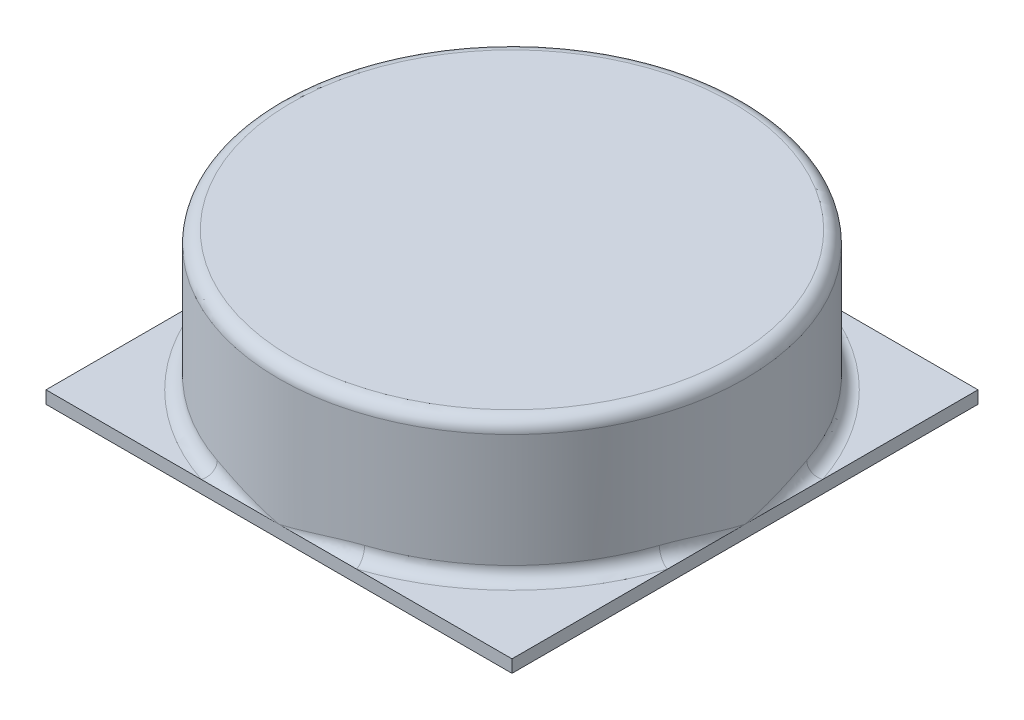
SolidWorks part; units mm, degrees
material "Inertia Wheel"
ref_plane "Piano frontale" through (0, 0, 0) normal (0, 0, 1) x (1, 0, 0)
ref_plane "Piano superiore" through (0, 0, 0) normal (0, 1, 0) x (1, 0, 0)
ref_plane "Piano destro" through (0, 0, 0) normal (1, 0, 0) x (0, 0, -1)
sketch "Schizzo1" plane through (0, 0, 0) normal (0, 1, 0) x (1, 0, 0)
  line L1 (-185, 185) -> (185, 185)
  line L2 (-185, 185) -> (-185, -185)
  line L3 (-185, -185) -> (185, -185)
  line L4 (185, 185) -> (185, -185)
  line L5 (-185, 185) -> (185, -185) construction
  line L6 (-185, -185) -> (185, 185) construction
  point P0 (0, 0)
  dimension "D1" = 370
extrude "Estrusione-Estrusione1" add sketch "Schizzo1" along normal blind 10
sketch "Schizzo2" plane through (0, 10, 0) normal (0, 1, 0) x (1, 0, 0)
  line L0 (185, -185) -> (185, 185) construction
  circle A0 centre (0, 0) radius 185
extrude "Estrusione-Estrusione2" add sketch "Schizzo2" along normal blind 110
fillet "Raccordo1" radius 10 5 edges at (130.8148, 10, 130.8148) (130.8148, 10, -130.8148) (-130.8148, 10, -130.8148) (-130.8148, 10, 130.8148) (0, 120, 185)
